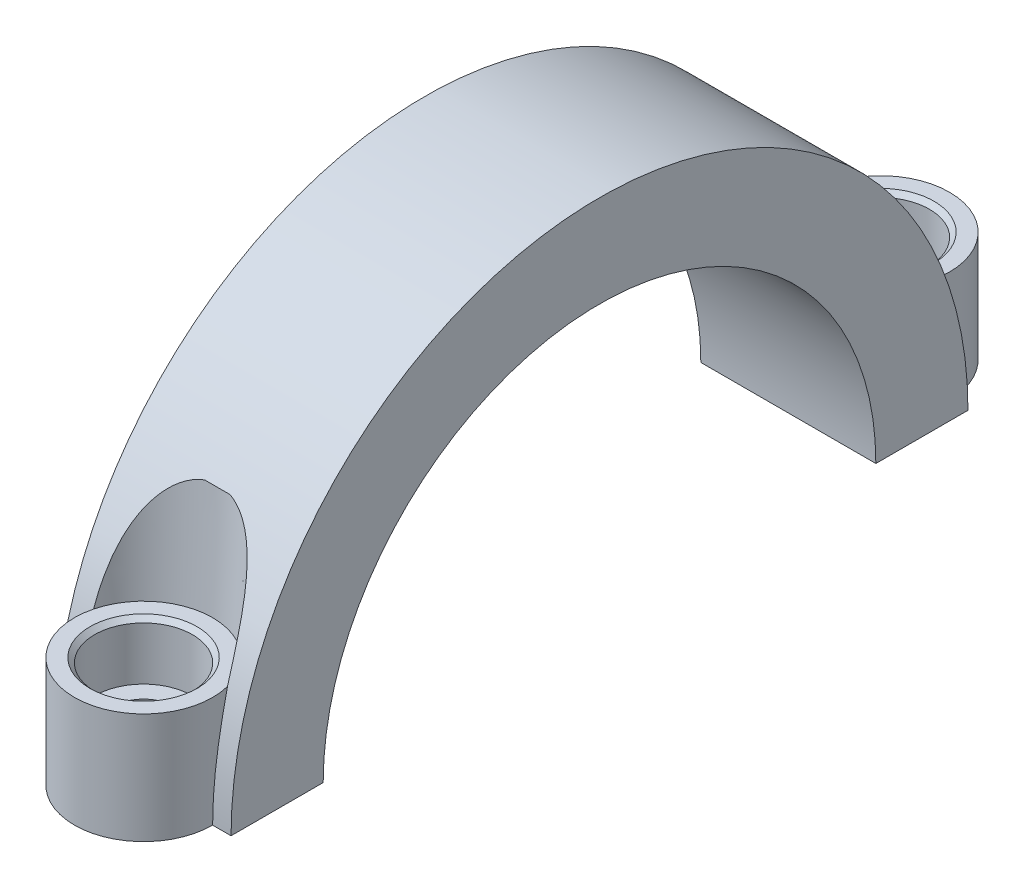
SolidWorks part; units mm, degrees
material "356.0-T6 Permanent Mold cast (SS)"
ref_plane "Front Plane" through (0, 0, 0) normal (0, 0, 1) x (1, 0, 0)
ref_plane "Top Plane" through (0, 0, 0) normal (0, 1, 0) x (1, 0, 0)
ref_plane "Right Plane" through (0, 0, 0) normal (1, 0, 0) x (0, 0, -1)
sketch "Sketch2" plane through (0, 0, 0) normal (1, 0, 0) x (0, 0, -1)
  line L0 (-50.8, 0) -> (-38.1, 0)
  line L1 (38.1, 0) -> (50.8, 0)
  arc A0 (38.1, 0) -> (-38.1, 0) centre (0, 0) ccw
  arc A1 (50.8, 0) -> (-50.8, 0) centre (0, 0) ccw
  circle A2 centre (0, 0) radius 50.8 construction
  circle A3 centre (0, 0) radius 38.1 construction
  dimension "D2" = 76.2
  dimension "D1" = 12.7
extrude "Boss-Extrude1" add sketch "Sketch2" along normal mid plane 24.13
sketch "Sketch6" plane through (0, 0, 0) normal (0, -1, 0) x (1, 0, 0)
  line L0 (12.065, -50.8) -> (-12.065, -50.8) construction
  circle A0 centre (0, -50.8) radius 9.525
  dimension "D1" = 19.05
extrude "Boss-Extrude2" add sketch "Sketch6" against normal blind 15.25
extrude "Cut-Extrude2" cut sketch "Sketch6<7>" against normal blind 15.25 draft 3 from offset 15.25 draft outward yes offset against normal yes
sketch "Sketch6<7>" plane through (0, 0, 0) normal (0, -1, 0) x (1, 0, 0) same geometry as "Sketch6"
hole_wizard "CBORE for 5/16 Socket Head Cap Screw1" positions "Sketch14" profile "Sketch15" counterbore size "5/16" standard "ANSI Inch" end condition through all
sketch "Sketch14" plane through (0, 15.25, 0) normal (0, 1, 0) x (1, 0, 0)
  point P0 (0, 50.8)
sketch "Sketch15" plane through (0, 15.25, -50.8) normal (1, 0, 0) x (0, 0, 1)
  line L0 (0, 0) -> (0, 15.25)
  line L1 (0, 15.25) -> (4.2164, 15.25)
  line L3 (4.2164, 15.25) -> (4.2164, 7.9375)
  line L4 (6.7475, 7.9375) -> (4.2164, 7.9375)
  line L5 (6.7475, 7.9375) -> (6.7475, 0.635)
  line L6 (6.7475, 0.635) -> (7.3825, 0)
  line L7 (7.3825, 0) -> (0, 0)
  line L8 (-6.7475, 0.635) -> (-7.3825, 0) construction
  line L11 (0, -6.35) -> (0, 107.95) construction
  dimension "Thru Hole Dia." = 8.4328
  dimension "Thru Hole Depth" = 15.25
  dimension "C'Bore Dia." = 13.495
  dimension "C'Bore Depth" = 7.9375
  dimension "Near C'Sink Dia." = 14.765
  dimension "Near C'Sink Angle" = 90
mirror "Mirror2" about plane through (0, 0, 0) normal (0, 0, 1) of "Cut-Extrude2", "CBORE for 5/16 Socket Head Cap Screw1", "Boss-Extrude2"
